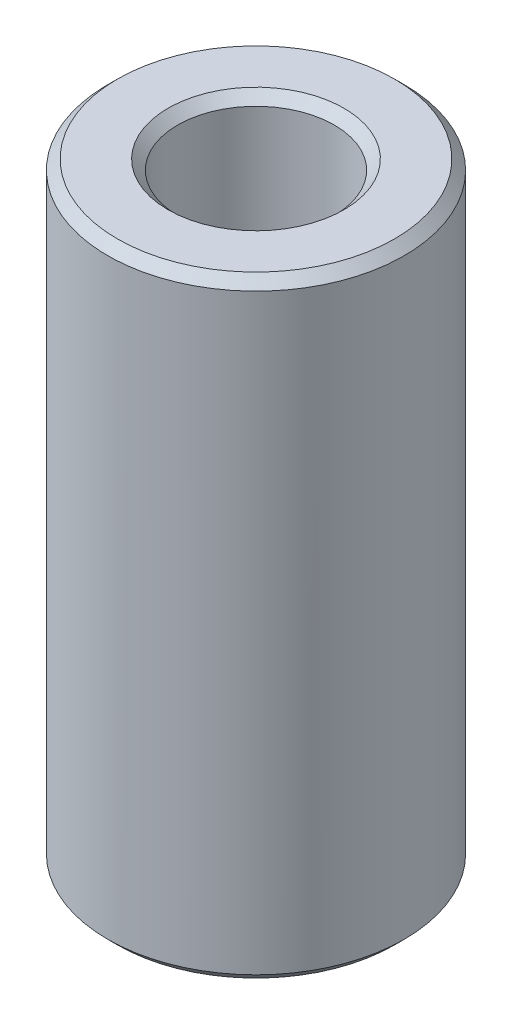
SolidWorks part; units mm, degrees
ref_plane "Front Plane" through (0, 0, 0) normal (0, 0, 1) x (1, 0, 0)
ref_plane "Top Plane" through (0, 0, 0) normal (0, 1, 0) x (1, 0, 0)
ref_plane "Right Plane" through (0, 0, 0) normal (1, 0, 0) x (0, 0, -1)
sketch "Sketch1" plane through (0, 0, 0) normal (0, 1, 0) x (1, 0, 0)
  circle A0 centre (0, 0) radius 60
  dimension "SLEEVE_OD" = 120
extrude "Boss-Extrude1" add sketch "Sketch1" along normal blind 247.5192
sketch "Sketch2" plane through (0, 0, 0) normal (0, 1, 0) x (1, 0, 0)
  circle A0 centre (0, 0) radius 31.6924
  dimension "BORE_D" = 63.3849
extrude "Cut-Extrude1" cut sketch "Sketch2" along normal through all
chamfer "Chamfer1" distance 3.9212 angle 45 4 edges at (0, 247.5192, 31.6924) (0, 0, 31.6924) (0, 0, 60) (0, 247.5192, 60)
